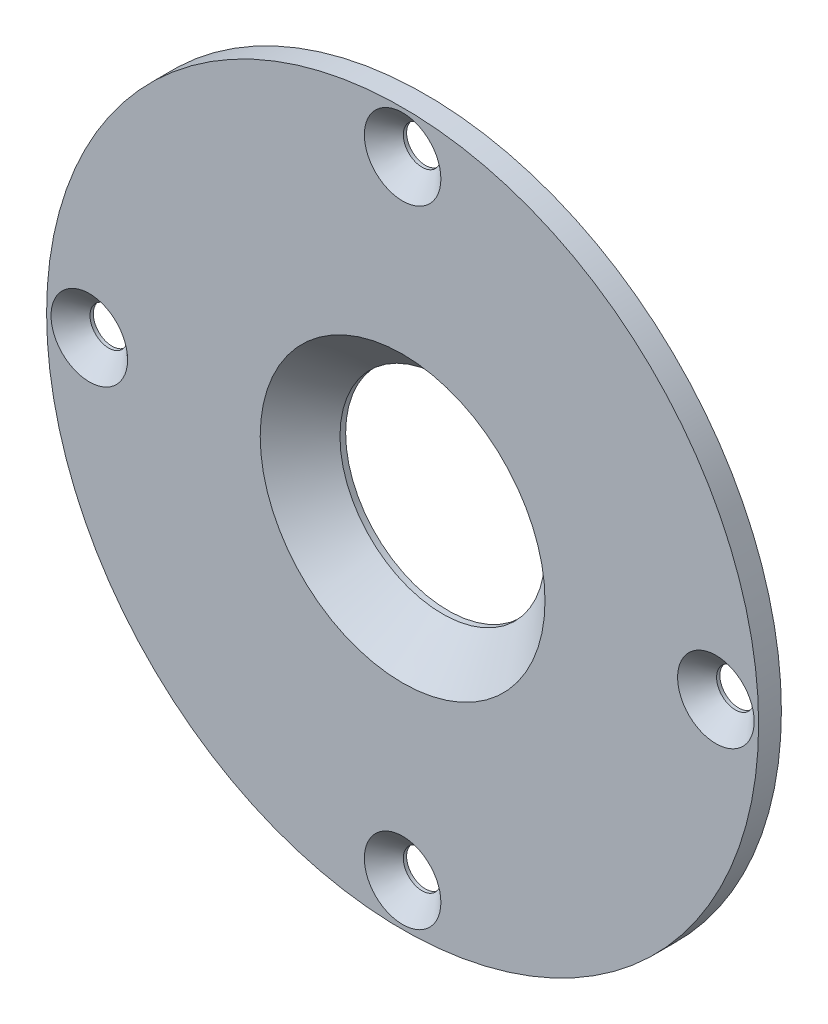
SolidWorks part; units mm, degrees
ref_plane "Płaszczyzna przednia" through (0, 0, 0) normal (0, 0, 1) x (1, 0, 0)
ref_plane "Płaszczyzna górna" through (0, 0, 0) normal (0, 1, 0) x (1, 0, 0)
ref_plane "Płaszczyzna prawa" through (0, 0, 0) normal (1, 0, 0) x (0, 0, -1)
sketch "Szkic1" plane through (0, 0, 0) normal (0, 1, 0) x (1, 0, 0)
  line L0 (0, 0) -> (18, 0)
  line L1 (18, 0) -> (18, -1)
  line L2 (18, -1) -> (25, -8)
  line L3 (25, -8) -> (0, -8)
  line L4 (0, -8) -> (0, 0)
  line L5 (0, -8) -> (0, 0) construction
sketch "Szkic2" plane through (0, 0, 0) normal (0, 1, 0) x (1, 0, 0)
  line L0 (0, 0) -> (45, 0)
  line L1 (45, 0) -> (45, -4)
  line L2 (45, -4) -> (62.5, -4)
  line L3 (62.5, -4) -> (62.5, -8)
  line L4 (62.5, -8) -> (0, -8)
  line L5 (0, -8) -> (0, 0)
  line L6 (0, -8) -> (0, 0) construction
revolve "Obrót1" add sketch "Szkic2" angle 360 about L6 reverse direction yes
revolve "Wycięcie-obrót1" cut sketch "Szkic1" angle 360 about L5 reverse direction yes
ref_plane "Płaszczyzna1" through (0, 0, 8) normal (0, 0, 1) x (1, 0, 0)
ref_plane "IP1 XY" through (0, 0, 8) normal (0, 0, 1) x (1, 0, 0)
ref_plane "IP1 XZ" through (0, 0, 0) normal (0, -1, 0) x (-1, 0, 0)
ref_plane "IP1 YZ" through (0, 0, 0) normal (1, 0, 0) x (0, 0, -1)
ref_axis "IP1 X" through (-80.9, 0, 8) along (1, 0, 0)
ref_axis "IP1 Y" through (0, -50, 8) along (0, 1, 0)
ref_axis "IP1 Z" through (0, 0, 80.9) along (0, 0, -1)
sketch3d "IP1"
  point P0 (0, 0, 8)
sketch "Szkic3" plane through (0, 0, 8) normal (0, 0, 1) x (1, 0, 0)
  circle A0 centre (0, 0) radius 55
  point P3 (-55, 0)
  point P4 (0, 55)
  point P5 (55, 0)
  point P6 (0, -55)
hole_wizard "Pogłębienie stożkowe pod M6 Wkręt z łbem stożkowym płaskim1" positions "Szkic 3D1" profile "Szkic4" countersink size "M6" standard "ISO"
sketch3d "Szkic 3D1"
  point P0 (-55, 0, 8)
  point P3 (0, 55, 8)
  point P6 (55, 0, 8)
  point P9 (0, -55, 8)
sketch "Szkic4" plane through (-55, 0, 8) normal (1, 0, 0) x (0, -1, 0)
  line L0 (0, 0) -> (0, 31.9828)
  line L1 (0, 31.9828) -> (3.3, 30)
  line L2 (3.3, 30) -> (3.3, 3.42)
  line L3 (3.3, 3.42) -> (6.72, 0)
  line L5 (6.72, 0) -> (0, 0)
  line L6 (-3.3, 3.42) -> (-6.72, 0) construction
  line L10 (0, 31.9828) -> (-3.3, 30) construction
  line L11 (0, -6.35) -> (0, 107.95) construction
  dimension "Średnica otworu" = 6.6
  dimension "Głębokośc otworu" = 30
  dimension "Średnica zewnętrznego pogłębienia stożkowego" = 13.44
  dimension "Kąt zewnętrznego pogłębienia stożkowego" = 90
  dimension "Kąt wiertła" = 118
